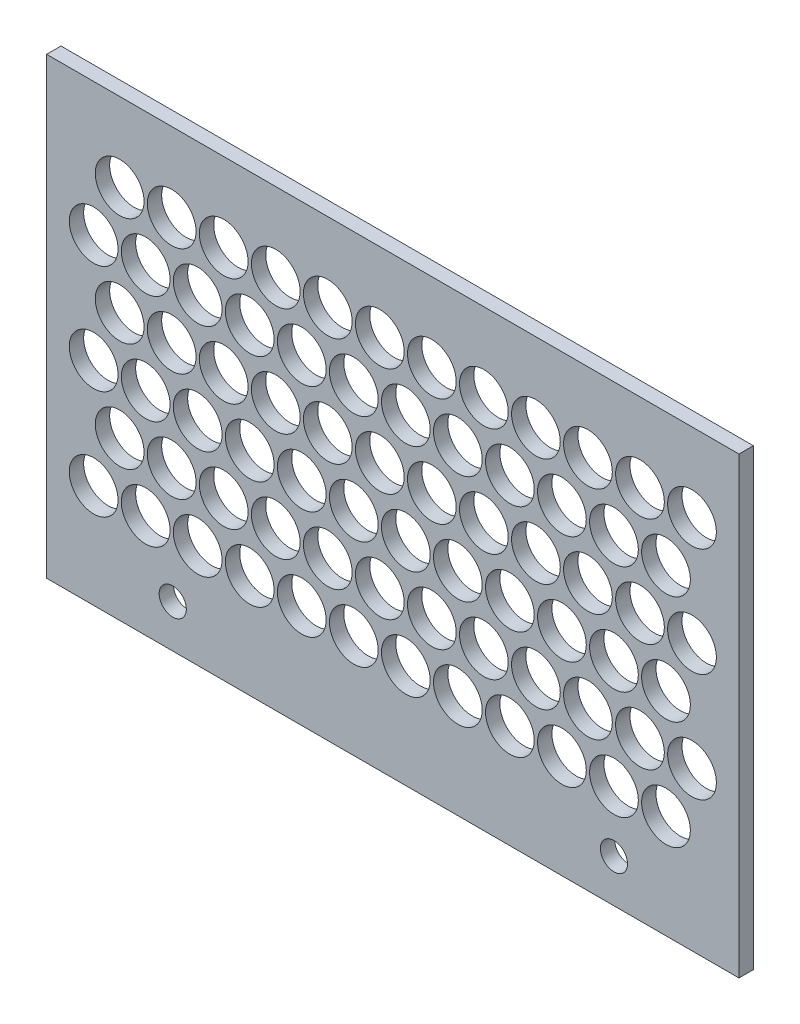
SolidWorks part; units mm, degrees
material "ABS"
ref_plane "X-Y Datum" through (0, 0, 0) normal (0, 0, 1) x (1, 0, 0)
ref_plane "X-Z Datum" through (0, 0, 0) normal (0, 1, 0) x (1, 0, 0)
ref_plane "Y-Z Datum" through (0, 0, 0) normal (1, 0, 0) x (0, 0, -1)
sketch "Sketch1" plane through (0, 0, 0) normal (0, 0, 1) x (1, 0, 0)
  line L1 (-143.025, 70.775) -> (143.025, 70.775)
  line L2 (-143.025, 70.775) -> (-143.025, -70.775)
  line L3 (-143.025, -70.775) -> (143.025, -70.775)
  line L4 (143.025, 70.775) -> (143.025, -70.775)
  line L5 (-143.025, 70.775) -> (143.025, -70.775) construction
  line L6 (-143.025, -70.775) -> (143.025, 70.775) construction
  line L13 (-153.025, -105.775) -> (153.025, -105.775)
  line L14 (-153.025, 91.65) -> (153.025, 91.65)
  line L15 (-153.025, 91.65) -> (-153.025, -105.775)
  line L16 (153.025, 91.65) -> (153.025, -105.775)
  line L17 (153.025, 70.775) -> (153.025, -70.775) construction
  line L18 (-143.025, 91.65) -> (143.025, 91.65) construction
  line L19 (-143.025, -105.775) -> (143.025, -105.775) construction
  line L20 (-153.025, 70.775) -> (-153.025, -70.775) construction
  line L21 (-132.25, -60) -> (-109.25, -60) construction
  circle A0 centre (-132.25, -60) radius 10.775
  circle A1 centre (-109.25, -60) radius 10.775 construction
  circle A2 centre (-120.75, -36) radius 10.775
  point P0 (0, 0)
  point P16 (-120.75, -60)
  dimension "D1" = 21.55
  dimension "D2" = 23
  dimension "D3" = 24
  dimension "D5" = 141.55
  dimension "D6" = 286.05
  dimension "D7" = 35
  dimension "D8" = 20.875
  dimension "D9" = 10
  dimension "D10" = 10
extrude "Boss-Extrude1" add sketch "Sketch1" along normal blind 6.35 contours A0 L3 L4 L1 L2 A2 | A2 | A0 | A0 L2 L3 | L1 L4 L3 L2 region at (2.4105, 0.9241, 0) region at (-140.6182, -68.3682, 0) region at (-132.25, -60, 0) region at (-149.383, -7.0625, 0) region at (-120.75, -36, 0)
sketch "Sketch3" plane through (0, 0, 6.35) normal (0, 0, 1) x (1, 0, 0)
  line L4 (143.025, 70.775) -> (-143.025, 70.775)
  line L5 (143.025, -70.775) -> (143.025, 70.775)
  line L6 (-143.025, -70.775) -> (143.025, -70.775)
  line L7 (-143.025, 70.775) -> (-143.025, -70.775)
  line L8 (143.025, 70.775) -> (-143.025, 70.775)
  line L9 (143.025, -70.775) -> (143.025, 70.775)
  line L10 (-143.025, -70.775) -> (143.025, -70.775)
  line L11 (-143.025, 70.775) -> (-143.025, -70.775)
  circle A1 centre (-120.75, -36) radius 10.775
  circle A2 centre (-120.75, -36) radius 10.775
  circle A3 centre (-132.25, -60) radius 10.775
  circle A4 centre (-132.25, -60) radius 10.775
  dimension "D1" = 0
  dimension "D2" = 0
  dimension "D3" = 0
extrude "Cut-Extrude1" cut sketch "Sketch3" against normal through all contours A4 region at (-132.25, -60, 6.35)
sketch "Sketch4" plane through (0, 0, 6.35) normal (0, 0, 1) x (1, 0, 0)
  line L4 (143.025, 70.775) -> (-143.025, 70.775)
  line L5 (143.025, -70.775) -> (143.025, 70.775)
  line L6 (-143.025, -70.775) -> (143.025, -70.775)
  line L7 (-143.025, 70.775) -> (-143.025, -70.775)
  line L8 (143.025, 70.775) -> (-143.025, 70.775)
  line L9 (143.025, -70.775) -> (143.025, 70.775)
  line L10 (-143.025, -70.775) -> (143.025, -70.775)
  line L11 (-143.025, 70.775) -> (-143.025, -70.775)
  circle A1 centre (-120.75, -36) radius 10.775
  circle A2 centre (-120.75, -36) radius 10.775
  circle A3 centre (-132.25, -60) radius 10.775
  circle A4 centre (-132.25, -60) radius 10.775
  dimension "D1" = 0
  dimension "D2" = 0
  dimension "D3" = 0
extrude "Cut-Extrude2" cut sketch "Sketch4" against normal through all contours A2 region at (-120.75, -36, 6.35)
pattern_linear "LPattern1" count 12 spacing 23 along (1, 0, 0) of "Cut-Extrude1", "Cut-Extrude2"
pattern_linear "LPattern2" count 3 spacing 48 along (0, 1, 0) of "LPattern1"
sketch "Sketch5" plane through (0, 0, 0) normal (0, 0, -1) x (-1, 0, 0)
sketch "Sketch13" plane through (0, 91.65, 0) normal (0, 1, 0) x (1, 0, 0)
  line L4 (153.025, 0) -> (-153.025, 0)
  line L5 (-153.025, 0) -> (-153.025, -6.35)
  line L6 (-153.025, -6.35) -> (153.025, -6.35)
  line L7 (153.025, -6.35) -> (153.025, 0)
  line L8 (153.025, 0) -> (-153.025, 0)
  line L9 (-153.025, 0) -> (-153.025, -6.35)
  line L10 (-153.025, -6.35) -> (153.025, -6.35)
  line L11 (153.025, -6.35) -> (153.025, 0)
  dimension "D1" = 0
extrude "Boss-Extrude2" add sketch "Sketch13" along normal blind 3.175
sketch "Sketch14" plane through (0, 0, 0) normal (0, 0, -1) x (-1, 0, 0)
  circle A0 centre (-97.75, -86.775) radius 6
  circle A1 centre (97.288, -86.775) radius 6
  dimension "D1" = 12
extrude "Cut-Extrude3" cut sketch "Sketch14" against normal through all
